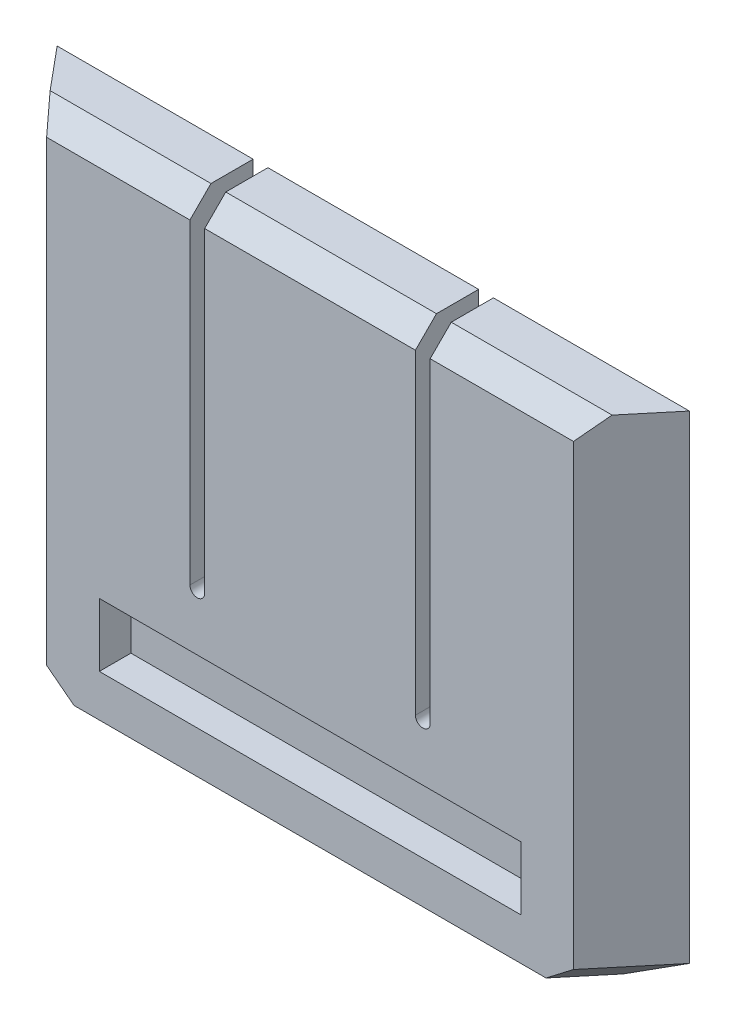
SolidWorks part; units mm, degrees
ref_plane "Front Plane" through (0, 0, 0) normal (0, 0, 1) x (1, 0, 0)
ref_plane "Top Plane" through (0, 0, 0) normal (0, 1, 0) x (1, 0, 0)
ref_plane "Right Plane" through (0, 0, 0) normal (1, 0, 0) x (0, 0, -1)
sketch "Sketch1" plane through (0, 0, 0) normal (0, 0, 1) x (1, 0, 0)
  line L1 (0, 0) -> (25, 0)
  line L2 (0, 0) -> (0, 23.7)
  line L3 (0, 23.7) -> (25, 23.7)
  line L4 (25, 0) -> (25, 23.7)
  dimension "D1" = 25
  dimension "D2" = 23.7
extrude "Boss-Extrude1" add sketch "Sketch1" along normal blind 3
sketch "Sketch2" plane through (0, 0, 0) normal (0, -1, 0) x (1, 0, 0)
  line L0 (0, 0) -> (-2.5, 0)
  line L1 (-2.5, 0) -> (0, 3)
  line L2 (25, 0) -> (27.5, 0)
  line L3 (27.5, 0) -> (25, 3)
  line L4 (25, 3) -> (25, 0) construction
  line L5 (0, 3) -> (0, 0)
  line L6 (25, 3) -> (25, 0)
  dimension "D1" = 2.5
  dimension "D2" = 2.5
extrude "Boss-Extrude2" add sketch "Sketch2" against normal blind 23.7
sketch "Sketch4" plane through (0, 0, 0) normal (0, 0, -1) x (-1, 0, 0)
  line L0 (-12.5, 23.7) -> (-12.5, 0) construction
  line L1 (-27.5, 23.7) -> (2.5, 23.7) construction
  line L2 (2.5, 0) -> (-27.5, 0) construction
  line L4 (-17.5, 17.7) -> (-7.5, 17.7)
  line L5 (-17.5, 17.7) -> (-17.5, 7.7)
  line L6 (-17.5, 7.7) -> (-7.5, 7.7)
  line L7 (-7.5, 17.7) -> (-7.5, 7.7)
  point P10 (-12.5, 7.7)
  dimension "D1" = 10
  dimension "D2" = 10
  dimension "D3" = 6
extrude "Cut-Extrude1" cut sketch "Sketch4" against normal blind 1.5
sketch "Sketch5" plane through (0, 0, 0) normal (0, 0, -1) x (-1, 0, 0)
  line L0 (-27.5, 23.7) -> (2.5, 23.7) construction
  line L2 (-17.5, 7.7) -> (-17.5, 23.7)
  line L3 (-17.5, 23.7) -> (-18.2, 23.7)
  line L4 (-18.2, 7.7) -> (-18.2, 23.7)
  line L7 (-7.5, 7.7) -> (-7.5, 23.7)
  line L8 (-7.5, 23.7) -> (-6.8, 23.7)
  line L9 (-6.8, 7.7) -> (-6.8, 23.7)
  arc A0 (-18.2, 7.7) -> (-17.5, 7.7) centre (-17.85, 7.7) ccw
  arc A1 (-6.8, 7.7) -> (-7.5, 7.7) centre (-7.15, 7.7) cw
  dimension "D1" = 0.7
  dimension "D2" = 0.7
extrude "Cut-Extrude2" cut sketch "Sketch5" against normal blind 3
sketch "Sketch6" plane through (0, 0, 0) normal (0, 0, -1) x (-1, 0, 0)
  line L0 (-7.5, 23.7) -> (-7.5, 17.7) construction
  line L1 (-17.5, 17.7) -> (-7.5, 17.7)
  line L2 (-17.5, 17.7) -> (-17.5, 20.7)
  line L3 (-17.5, 20.7) -> (-7.5, 20.7)
  line L4 (-7.5, 17.7) -> (-7.5, 20.7)
extrude "Boss-Extrude3" add sketch "Sketch6" along normal blind 1.5
chamfer "Chamfer1" distance 1.5 angle 60 1 edges at (12.5, 17.7, -1.5) first distance on face at (12.5, 17.7, 0)
sketch "Sketch7" plane through (0, 0, 3) normal (0, 0, 1) x (1, 0, 0)
  line L0 (0, 0) -> (25, 0) construction
  line L1 (2.5, 5) -> (22.5, 5)
  line L2 (2.5, 5) -> (2.5, 2)
  line L3 (2.5, 2) -> (22.5, 2)
  line L4 (22.5, 5) -> (22.5, 2)
  point P6 (12.5, 0)
  point P7 (12.5, 2)
  dimension "D1" = 3
  dimension "D2" = 20
  dimension "D3" = 2
extrude "Cut-Extrude3" cut sketch "Sketch7" against normal blind 1.5
fillet "Fillet1" radius 1 2 edges at (12.5, 17.7, 1.5) (12.5, 7.7, 1.5)
sketch "Sketch8" plane through (0, 0, 0) normal (0, 0, -1) x (-1, 0, 0)
  line L0 (-7.5, 20.7) -> (-17.5, 20.7) construction
  line L1 (-16.5, 22.7) -> (-8.5, 22.7)
  line L2 (-16.5, 22.7) -> (-16.5, 20.7)
  line L3 (-16.5, 20.7) -> (-8.5, 20.7)
  line L4 (-8.5, 22.7) -> (-8.5, 20.7)
  line L5 (-17.5, 20.7) -> (-17.5, 23.7) construction
  line L6 (-7.5, 23.7) -> (-7.5, 20.7) construction
  line L7 (-17.5, 23.7) -> (-7.5, 23.7) construction
  dimension "D1" = 1
  dimension "D2" = 1
  dimension "D3" = 1
extrude "Cut-Extrude4" cut sketch "Sketch8" against normal blind 1
fillet "Fillet2" radius 10 1 edges at (12.5, 17.7, 0)
fillet "Fillet3" radius 1 1 edges at (12.5, 7.7, 0)
chamfer "Chamfer3" distance 1 angle 45 3 edges at (-1.25, 0, 1.5) (26.25, 0, 1.5) (12.5, 0, 0)
chamfer "Chamfer4" distance 1 angle 45 3 edges at (21.6, 23.7, 3) (12.5, 23.7, 3) (3.4, 23.7, 3)
chamfer "Chamfer5" distance 1 angle 50 1 edges at (12.5, 20.7, 1) first distance on face at (12.5, 20.7, -0.125)
